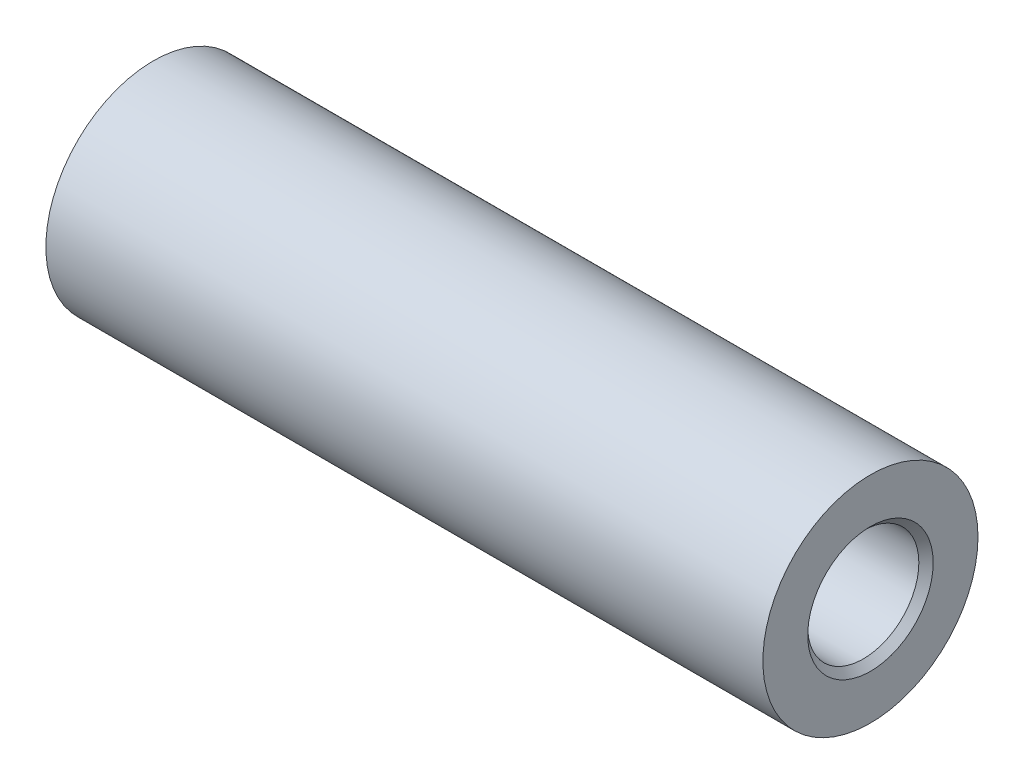
SolidWorks part; units mm, degrees
ref_plane "前视基准面" through (0, 0, 0) normal (0, 0, 1) x (1, 0, 0)
ref_plane "上视基准面" through (0, 0, 0) normal (0, 1, 0) x (1, 0, 0)
ref_plane "右视基准面" through (0, 0, 0) normal (1, 0, 0) x (0, 0, -1)
other "Configuration Table"
sketch "草图1" plane through (0, 0, 0) normal (1, 0, 0) x (0, 0, -1)
  circle A0 centre (0, 0) radius 6
  dimension "D1" = 12
extrude "凸台-拉伸1" add sketch "草图1" along normal blind 19 and the other way blind 21
sketch "草图3" plane through (19, 0, 0) normal (1, 0, 0) x (0, 0, -1)
  circle A0 centre (0, 0) radius 3.1
  dimension "D1" = 6.2
extrude "切除-拉伸1" cut sketch "草图3" against normal blind 17
sketch "草图4" plane through (-21, 0, 0) normal (-1, 0, 0) x (0, 0, 1)
  circle A0 centre (0, 0) radius 4.1
  dimension "D1" = 8.2
extrude "切除-拉伸2" cut sketch "草图4" against normal blind 21
sketch "草图5" plane through (2, 0, 0) normal (1, 0, 0) x (0, 0, -1)
  line L0 (-1.6882, 2.6) -> (1.6882, 2.6)
  circle A0 centre (0, 0) radius 3.1 construction
  arc A1 (1.6882, 2.6) -> (-1.6882, 2.6) centre (0, 0) ccw
  arc A2 (-1.6882, 2.6) -> (1.6882, 2.6) centre (0, 0) ccw construction
  dimension "D1" = 2.6
extrude "凸台-拉伸2" add sketch "草图5" along normal blind 12
sketch "草图6" plane through (0, 0, 0) normal (-1, 0, 0) x (0, 0, 1)
  line L0 (-1.7482, 3.7086) -> (2.1694, 3.4791)
  circle A0 centre (0, 0) radius 4.1 construction
  arc A1 (2.1694, 3.4791) -> (-1.7482, 3.7086) centre (0, 0) ccw
  arc A2 (-1.7482, 3.7086) -> (2.1694, 3.4791) centre (0, 0) ccw construction
  dimension "D1" = 3.6
extrude "凸台-拉伸3" add sketch "草图6" along normal blind 15
chamfer "倒角1" distance 0.4 angle 45 2 edges at (19, 0, -3.1) (-21, 0, 4.1)
chamfer "倒角2" distance 0.5 angle 45 2 edges at (-15, 3.5938, 0.2106) (14, 2.6, 0)
